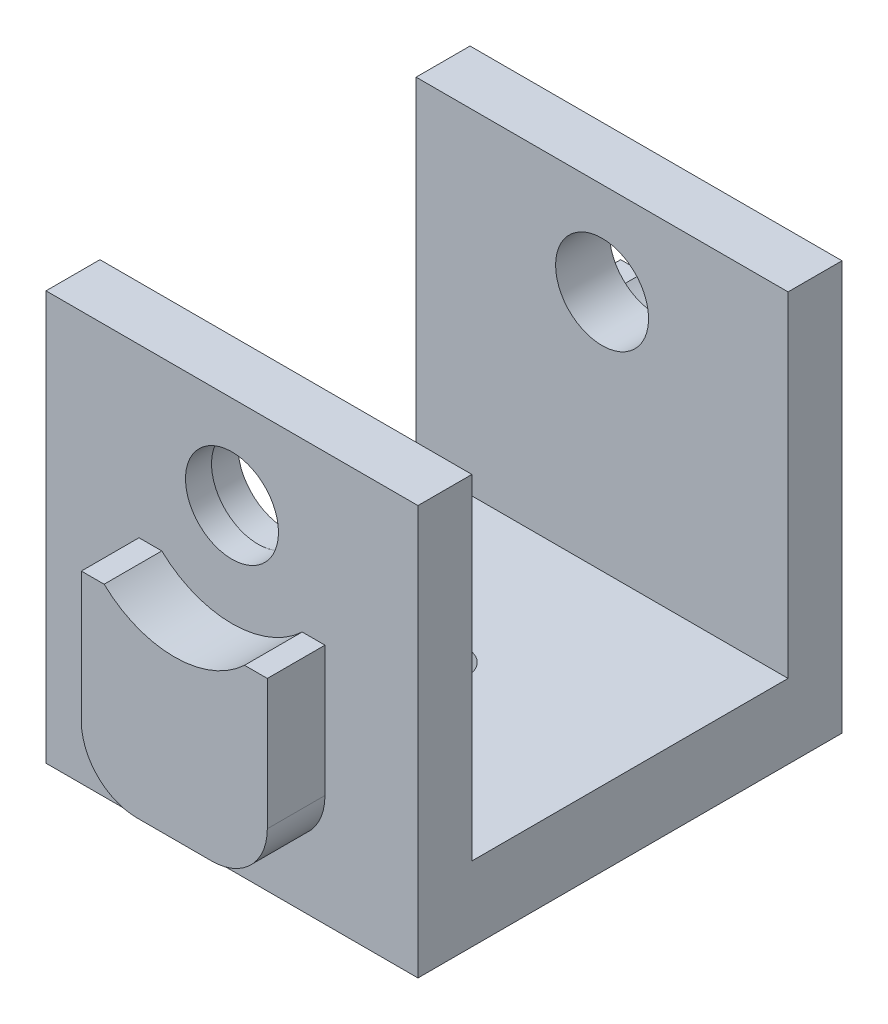
SolidWorks part; units mm, degrees
material "PLA"
ref_plane "Front Plane" through (0, 0, 0) normal (0, 0, 1) x (1, 0, 0)
ref_plane "Top Plane" through (0, 0, 0) normal (0, 1, 0) x (1, 0, 0)
ref_plane "Right Plane" through (0, 0, 0) normal (1, 0, 0) x (0, 0, -1)
ref_plane "Plane16" through (0, 32, 0) normal (0, -1, 0) x (-1, 0, 0)
ref_plane "Plane17" through (20.1, 0, 0) normal (1, 0, 0) x (0, 0, -1)
sketch "Sketch114" plane through (20.1, 0, 0) normal (1, 0, 0) x (0, 0, -1)
  line L0 (-2.9, 37) -> (-22.9, 37)
  line L1 (-22.9, 37) -> (-22.9, 15)
  line L2 (-22.9, 15) -> (-2.9, 15)
  line L3 (-2.9, 15) -> (-2.9, 37)
extrude "Boss-Extrude16" add sketch "Sketch114" against normal blind 20 separate body
sketch "Sketch115" plane through (0.1, 0, 0) normal (-1, 0, 0) x (0, 0, 1)
  line L0 (21.4, 37) -> (4.4, 37)
  line L1 (4.4, 37) -> (4.4, 19)
  line L2 (4.4, 19) -> (21.4, 19)
  line L3 (21.4, 19) -> (21.4, 37)
  line L4 (2.9, 15) -> (2.9, 37) construction
  line L5 (22.9, 15) -> (2.9, 15) construction
  dimension "D1" = 1.5
  dimension "D2" = 18.5
  dimension "D3" = 4
  dimension "D4" = 22
extrude "Cut-Extrude6" cut sketch "Sketch115" against normal through all
ref_plane "Plane18" through (0, 0, 22.9) normal (0, 0, 1) x (1, 0, 0)
sketch "Sketch121" plane through (0, 0, 22.9) normal (0, 0, 1) x (1, 0, 0)
  line L0 (5.1, 28) -> (6.3251, 28)
  line L1 (13.8749, 28) -> (15.1, 28)
  line L2 (15.1, 28) -> (15.1, 18)
  line L3 (15.1, 18) -> (5.1, 18)
  line L4 (5.1, 18) -> (5.1, 28)
  arc A0 (6.3251, 28) -> (13.8749, 28) centre (10.1, 32) ccw
extrude "Boss-Extrude17" add sketch "Sketch121" along normal blind 3.1 separate body
sketch "Sketch122" plane through (0, 0, 2.9) normal (0, 0, -1) x (-1, 0, 0)
  line L0 (-15.1, 18) -> (-15.1, 28)
  line L1 (-15.1, 28) -> (-13.8749, 28)
  line L2 (-6.3251, 28) -> (-5.1, 28)
  line L3 (-5.1, 28) -> (-5.1, 18)
  line L4 (-5.1, 18) -> (-15.1, 18)
  arc A0 (-13.8749, 28) -> (-6.3251, 28) centre (-10.1, 32) ccw
extrude "Boss-Extrude18" add sketch "Sketch122" along normal blind 3.1
hole_wizard "Ø5.0 (5) Diameter Hole1" positions "Sketch124" profile "Sketch123" hole size "Ø5.0" standard "ANSI Metric" end condition up to next
sketch "Sketch124" plane through (0, 0, 2.9) normal (0, 0, -1) x (-1, 0, 0)
  point P0 (-10.1, 32)
sketch "Sketch123" plane through (10.1, 32, 2.9) normal (1, 0, 0) x (0, 1, 0)
  line L0 (0, 0) -> (0, 1.501)
  line L1 (0, 1.501) -> (2.5, 1.501)
  line L2 (2.5, 1.501) -> (2.5, 0)
  line L5 (2.5, 0) -> (0, 0)
  line L11 (0, -6.35) -> (0, 107.95) construction
  dimension "Thru Hole Dia." = 5
  dimension "Thru Hole Depth" = 1.501
hole_wizard "Ø1.0mm Dowel Hole1" positions "Sketch126" profile "Sketch125" hole size "Ø1.0" standard "ANSI Metric"
sketch "Sketch126" plane through (0, 15, 0) normal (0, -1, 0) x (-1, 0, 0)
  point P0 (-10.1, -12.9)
sketch "Sketch125" plane through (10.1, 15, 12.9) normal (1, 0, 0) x (0, 0, -1)
  line L0 (0, 0) -> (0, 4)
  line L1 (0, 4) -> (1.2645, 4)
  line L2 (1.2645, 4) -> (1.2645, 0)
  line L5 (1.2645, 0) -> (0, 0)
  line L10 (0, 4) -> (-1.2645, 4) construction
  line L11 (0, -6.35) -> (0, 107.95) construction
  dimension "Hole Dia." = 2.529
  dimension "Hole Depth" = 4
  dimension "Drill Angle" = 180
fillet "Fillet6" radius 3 2 edges at (15.1, 18, 24.45) (5.1, 18, 24.45) tangent propagation no
fillet "Fillet7" radius 3 2 edges at (5.1, 18, 1.35) (15.1, 18, 1.35)
hole_wizard "Ø5.1 (5.1) Diameter Hole1" positions "Sketch127" profile "Sketch128" hole size "Ø5.1" standard "ANSI Metric" end condition through all
sketch "Sketch127" plane through (0, 0, 21.4) normal (0, 0, -1) x (-1, 0, 0)
  point P0 (-10.0693, 31.998)
sketch "Sketch128" plane through (10.0693, 31.998, 21.4) normal (1, 0, 0) x (0, 1, 0)
  line L0 (0, 0) -> (0, 4.6)
  line L1 (0, 4.6) -> (2.55, 4.6)
  line L2 (2.55, 4.6) -> (2.55, 0)
  line L5 (2.55, 0) -> (0, 0)
  line L11 (0, -6.35) -> (0, 107.95) construction
  dimension "Thru Hole Dia." = 5.1
  dimension "Thru Hole Depth" = 4.6
sketch "Sketch130" plane through (0, 0, 2.9) normal (0, 0, -1) x (-1, 0, 0)
  line L4 (-20.1, 37) -> (-20.1, 15)
  line L5 (-20.1, 15) -> (-0.1, 15)
  line L6 (-0.1, 15) -> (-0.1, 37)
  line L7 (-0.1, 37) -> (-20.1, 37)
  line L8 (-20.1, 37) -> (-20.1, 15)
  line L9 (-20.1, 15) -> (-0.1, 15)
  line L10 (-0.1, 15) -> (-0.1, 37)
  line L11 (-0.1, 37) -> (-20.1, 37)
  circle A0 centre (-10.1, 32) radius 2.5
  dimension "D1" = 0
extrude "Boss-Extrude19" add sketch "Sketch130" along normal blind 1.4
sketch "Sketch131" plane through (0, 0, 22.9) normal (0, 0, 1) x (1, 0, 0)
  line L4 (20.1, 15) -> (20.1, 37)
  line L5 (20.1, 37) -> (0.1, 37)
  line L6 (0.1, 37) -> (0.1, 15)
  line L7 (0.1, 15) -> (20.1, 15)
  line L8 (20.1, 15) -> (20.1, 37)
  line L9 (20.1, 37) -> (0.1, 37)
  line L10 (0.1, 37) -> (0.1, 15)
  line L11 (0.1, 15) -> (20.1, 15)
  circle A0 centre (10.1, 32) radius 2.5
  dimension "D1" = 0
extrude "Boss-Extrude20" add sketch "Sketch131" along normal blind 1.4
sketch "Sketch132" plane through (0, 0, 26) normal (0, 0, 1) x (1, 0, 0)
  line L5 (8.1, 18) -> (12.1, 18)
  line L6 (15.1, 21) -> (15.1, 28)
  line L7 (15.1, 28) -> (13.8749, 28)
  line L8 (6.3251, 28) -> (5.1, 28)
  line L9 (5.1, 28) -> (5.1, 21)
  line L10 (8.1, 18) -> (12.1, 18)
  line L11 (15.1, 21) -> (15.1, 28)
  line L12 (15.1, 28) -> (13.8749, 28)
  line L13 (6.3251, 28) -> (5.1, 28)
  line L14 (5.1, 28) -> (5.1, 21)
  arc A3 (12.1, 18) -> (15.1, 21) centre (12.1, 21) ccw
  arc A4 (6.3251, 28) -> (13.8749, 28) centre (10.1, 32) ccw
  arc A5 (5.1, 21) -> (8.1, 18) centre (8.1, 21) ccw
  arc A6 (12.1, 18) -> (15.1, 21) centre (12.1, 21) ccw
  arc A7 (6.3251, 28) -> (13.8749, 28) centre (10.1, 32) ccw
  arc A8 (5.1, 21) -> (8.1, 18) centre (8.1, 21) ccw
  dimension "D1" = 0
extrude "Boss-Extrude21" add sketch "Sketch132" along normal blind 1.4
sketch "Sketch133" plane through (0, 0, -0.2) normal (0, 0, -1) x (-1, 0, 0)
  line L5 (-12.1, 18) -> (-8.1, 18)
  line L6 (-5.1, 21) -> (-5.1, 28)
  line L7 (-5.1, 28) -> (-6.3251, 28)
  line L8 (-13.8749, 28) -> (-15.1, 28)
  line L9 (-15.1, 28) -> (-15.1, 21)
  line L10 (-12.1, 18) -> (-8.1, 18)
  line L11 (-5.1, 21) -> (-5.1, 28)
  line L12 (-5.1, 28) -> (-6.3251, 28)
  line L13 (-13.8749, 28) -> (-15.1, 28)
  line L14 (-15.1, 28) -> (-15.1, 21)
  arc A3 (-8.1, 18) -> (-5.1, 21) centre (-8.1, 21) ccw
  arc A4 (-13.8749, 28) -> (-6.3251, 28) centre (-10.1, 32) ccw
  arc A5 (-15.1, 21) -> (-12.1, 18) centre (-12.1, 21) ccw
  arc A6 (-8.1, 18) -> (-5.1, 21) centre (-8.1, 21) ccw
  arc A7 (-13.8749, 28) -> (-6.3251, 28) centre (-10.1, 32) ccw
  arc A8 (-15.1, 21) -> (-12.1, 18) centre (-12.1, 21) ccw
  dimension "D1" = 0
extrude "Boss-Extrude22" add sketch "Sketch133" along normal blind 1.4
sketch "Sketch134" plane through (0, 15, 0) normal (0, -1, 0) x (1, 0, 0)
  line L0 (9.5655, 16.0301) -> (8.3437, 15.0161) construction
  line L1 (8.3437, 15.0161) -> (7.122, 14.0022) construction
  line L2 (7.122, 14.0022) -> (7.3892, 12.4371) construction
  line L3 (7.3892, 12.4371) -> (7.6565, 10.872) construction
  line L4 (9.5655, 16.0301) -> (8.3437, 15.0161)
  line L5 (8.3437, 15.0161) -> (7.122, 14.0022)
  line L6 (7.122, 14.0022) -> (7.3892, 12.4371)
  line L7 (7.3892, 12.4371) -> (7.6565, 10.872)
  line L8 (11.0545, 15.479) -> (9.5655, 16.0301) construction
  line L9 (12.5435, 14.928) -> (11.0545, 15.479) construction
  line L10 (12.8108, 13.3629) -> (12.5435, 14.928) construction
  line L11 (13.078, 11.7978) -> (12.8108, 13.3629) construction
  line L12 (11.8563, 10.7839) -> (13.078, 11.7978) construction
  line L13 (10.6345, 9.7699) -> (11.8563, 10.7839) construction
  line L14 (7.6565, 10.872) -> (9.1455, 10.321) construction
  line L15 (9.1455, 10.321) -> (10.6345, 9.7699) construction
  line L16 (11.0545, 15.479) -> (9.5655, 16.0301)
  line L17 (12.5435, 14.928) -> (11.0545, 15.479)
  line L18 (12.8108, 13.3629) -> (12.5435, 14.928)
  line L19 (13.078, 11.7978) -> (12.8108, 13.3629)
  line L20 (11.8563, 10.7839) -> (13.078, 11.7978)
  line L21 (10.6345, 9.7699) -> (11.8563, 10.7839)
  line L22 (7.6565, 10.872) -> (9.1455, 10.321)
  line L23 (9.1455, 10.321) -> (10.6345, 9.7699)
extrude "Cut-Extrude7" cut sketch "Sketch134" against normal blind 2
